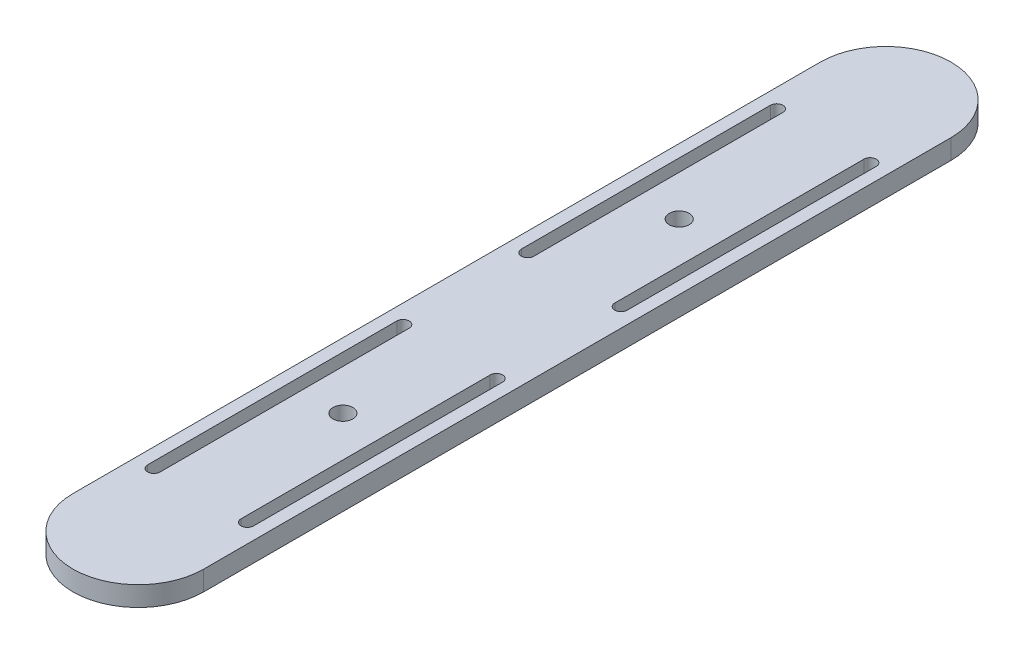
SolidWorks part; units mm, degrees
ref_plane "Front Plane" through (0, 0, 0) normal (0, 0, 1) x (1, 0, 0)
ref_plane "Top Plane" through (0, 0, 0) normal (0, 1, 0) x (1, 0, 0)
ref_plane "Right Plane" through (0, 0, 0) normal (1, 0, 0) x (0, 0, -1)
sketch "Sketch1" plane through (0, 0, 0) normal (0, 1, 0) x (1, 0, 0)
  line L0 (-10.5, 0) -> (-10.5, -120)
  line L1 (10.5, 0) -> (10.5, -120)
  arc A0 (10.5, 0) -> (-10.5, 0) centre (0, 0) ccw
  arc A1 (-10.5, -120) -> (10.5, -120) centre (0, -120) ccw
  dimension "D1" = 10.5
  dimension "D2" = 120
extrude "Boss-Extrude1" add sketch "Sketch1" along normal blind 3.175
sketch "Sketch3" plane through (0, 0, 0) normal (0, -1, 0) x (1, 0, 0)
  line L0 (-8.5, 110) -> (-8.5, 70) construction
  line L1 (-6.5, 70) -> (-6.5, 110) construction
  line L2 (6.5, 110) -> (6.5, 70) construction
  line L3 (8.5, 70) -> (8.5, 110) construction
  line L4 (8.5, 10) -> (8.5, 50) construction
  line L5 (6.5, 50) -> (6.5, 10) construction
  line L6 (-8.5, 50) -> (-8.5, 10) construction
  line L7 (-6.5, 10) -> (-6.5, 50) construction
  line L8 (-8.5, 110) -> (-8.5, 70)
  line L9 (-6.5, 70) -> (-6.5, 110)
  line L10 (6.5, 110) -> (6.5, 70)
  line L11 (8.5, 70) -> (8.5, 110)
  line L12 (8.5, 10) -> (8.5, 50)
  line L13 (6.5, 50) -> (6.5, 10)
  line L14 (-8.5, 50) -> (-8.5, 10)
  line L15 (-6.5, 10) -> (-6.5, 50)
  arc A1 (-8.5, 70) -> (-6.5, 70) centre (-7.5, 70) ccw construction
  arc A2 (8.5, 110) -> (6.5, 110) centre (7.5, 110) ccw construction
  arc A3 (6.5, 70) -> (8.5, 70) centre (7.5, 70) ccw construction
  arc A4 (6.5, 10) -> (8.5, 10) centre (7.5, 10) ccw construction
  arc A5 (8.5, 50) -> (6.5, 50) centre (7.5, 50) ccw construction
  arc A6 (-6.5, 50) -> (-8.5, 50) centre (-7.5, 50) ccw construction
  arc A7 (-8.5, 10) -> (-6.5, 10) centre (-7.5, 10) ccw construction
  arc A8 (-8.5, 70) -> (-6.5, 70) centre (-7.5, 70) ccw
  arc A9 (8.5, 110) -> (6.5, 110) centre (7.5, 110) ccw
  arc A10 (6.5, 70) -> (8.5, 70) centre (7.5, 70) ccw
  arc A11 (6.5, 10) -> (8.5, 10) centre (7.5, 10) ccw
  arc A12 (8.5, 50) -> (6.5, 50) centre (7.5, 50) ccw
  arc A13 (-6.5, 50) -> (-8.5, 50) centre (-7.5, 50) ccw
  arc A14 (-8.5, 10) -> (-6.5, 10) centre (-7.5, 10) ccw
  arc A15 (-6.5, 110) -> (-8.5, 110) centre (-7.5, 110) ccw construction
  arc A16 (-6.5, 110) -> (-8.5, 110) centre (-7.5, 110) ccw
extrude "Cut-Extrude2" cut sketch "Sketch3" against normal through all both and the other way through all
sketch "Sketch4" plane through (0, 3.175, 0) normal (0, 1, 0) x (1, 0, 0)
  circle A0 centre (0, -33.15) radius 1.6 construction
  circle A1 centre (0, -87.15) radius 1.6 construction
  circle A2 centre (0, -33.15) radius 1.6
  circle A3 centre (0, -87.15) radius 1.6
extrude "Cut-Extrude3" cut sketch "Sketch4" against normal through all both and the other way through all
